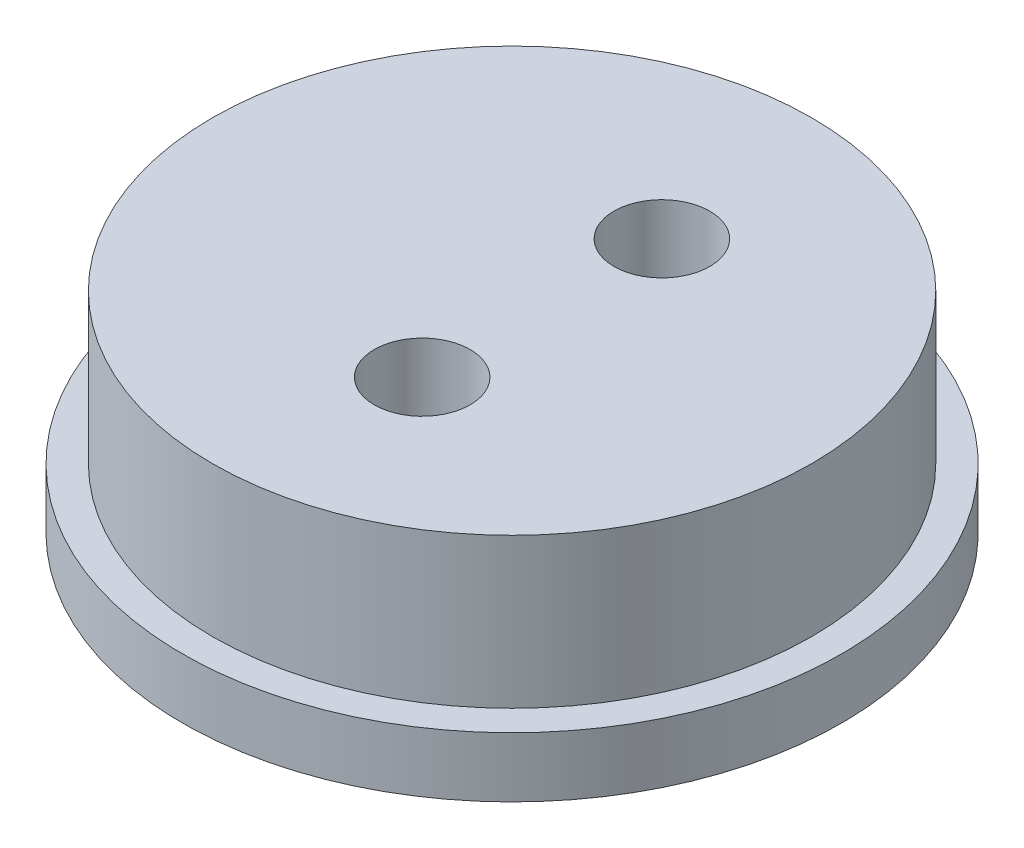
SolidWorks part; units mm, degrees
ref_plane "Front Plane" through (0, 0, 0) normal (0, 0, 1) x (1, 0, 0)
ref_plane "Top Plane" through (0, 0, 0) normal (0, 1, 0) x (1, 0, 0)
ref_plane "Right Plane" through (0, 0, 0) normal (1, 0, 0) x (0, 0, -1)
sketch "Sketch1" plane through (0, 0, 0) normal (0, 1, 0) x (1, 0, 0)
  line L0 (0, 0) -> (-1, 0) construction
  circle A1 centre (-1, 0) radius 10
  point P12 (0, 0)
  dimension "D3" = 20
  dimension "D2" = 1
extrude "Boss-Extrude1" add sketch "Sketch1" along normal blind 7
sketch "Sketch2" plane through (0, 0, 0) normal (0, -1, 0) x (1, 0, 0)
  line L0 (-12.8187, 0) -> (7.6603, 0) construction
  circle A0 centre (-1, 0) radius 11
  dimension "D2" = 22
  dimension "D1" = 1
extrude "Boss-Extrude2" add sketch "Sketch2" against normal blind 2
sketch "Sketch4" plane through (0, 7, 0) normal (0, 1, 0) x (1, 0, 0)
  line L0 (0, 8.8969) -> (0, -8.7328) construction
  circle A0 centre (0, 0) radius 4 construction
  circle A1 centre (0, 4) radius 1.6
  circle A2 centre (0, -4) radius 1.6
  dimension "D1" = 8
  dimension "D2" = 3.2
extrude "Cut-Extrude1" cut sketch "Sketch4" against normal through all
